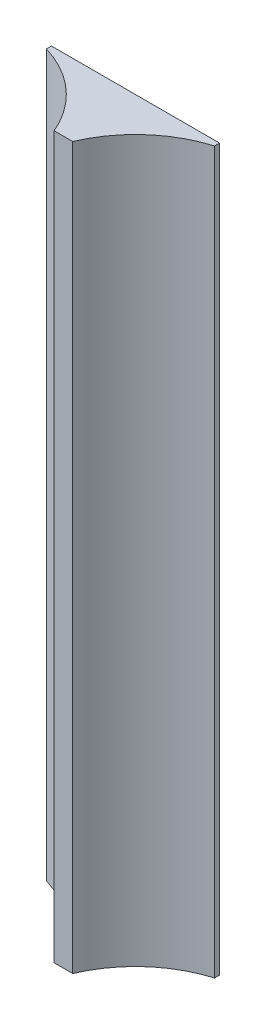
SolidWorks part; units mm, degrees
ref_plane "Front" through (0, 0, 0) normal (0, 0, 1) x (1, 0, 0)
ref_plane "Top" through (0, 0, 0) normal (0, 1, 0) x (1, 0, 0)
ref_plane "Right" through (0, 0, 0) normal (1, 0, 0) x (0, 0, -1)
sketch "Sketch1" plane through (0, 0, 0) normal (0, 1, 0) x (1, 0, 0)
  line L0 (-0.7751, 0) -> (0.7751, 0)
  line L1 (7, 5.5851) -> (7, 6)
  line L2 (7, 6) -> (-7, 6)
  line L3 (-7, 6) -> (-7, 5.5851)
  arc A0 (0.7751, 0) -> (7, 5.5851) centre (9.825, -3.825) cw
  arc A1 (-7, 5.5851) -> (-0.7751, 0) centre (-9.825, -3.825) cw
  point P9 (0, 6)
  point P10 (0, 0)
  dimension "D1" = 9.825
  dimension "D6" = 6
  dimension "D2" = 19.65
  dimension "D3" = 9.825
  dimension "D4" = 14
extrude "Boss-Extrude1" add sketch "Sketch1" along normal blind 60
sketch "Sketch3" plane through (0, 0, -6) normal (0, 0, -1) x (-1, 0, 0)
  line L0 (0, 0) -> (0, 60) construction
  line L1 (-7, 0) -> (7, 0) construction
  line L2 (-7, 60) -> (7, 60) construction
  point P6 (0, 45)
  point P7 (0, 15)
  dimension "D1" = 15
  dimension "D2" = 15
